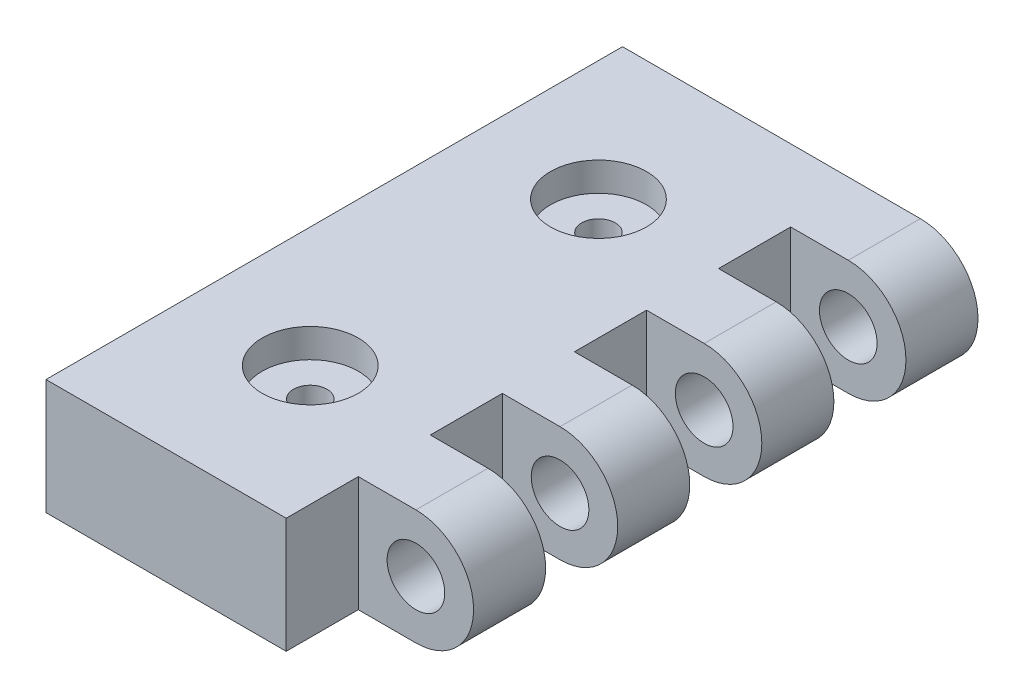
SolidWorks part; units mm, degrees
ref_plane "Front" through (0, 0, 0) normal (0, 0, 1) x (1, 0, 0)
ref_plane "Top" through (0, 0, 0) normal (0, 1, 0) x (1, 0, 0)
ref_plane "Right" through (0, 0, 0) normal (1, 0, 0) x (0, 0, -1)
sketch "Sketch1" plane through (0, 0, 0) normal (0, 1, 0) x (1, 0, 0)
  line L1 (0, 0) -> (-25, 0)
  line L2 (0, 0) -> (0, 60)
  line L3 (0, 60) -> (-25, 60)
  line L4 (-25, 0) -> (-25, 60)
  dimension "D1" = 60
  dimension "D2" = 25
extrude "Boss-Extrude1" add sketch "Sketch1" along normal blind 12
sketch "Sketch2" plane through (0, 0, 0) normal (0, 0, 1) x (1, 0, 0)
  line L0 (0, 0) -> (13.9056, 0) construction
  line L1 (0, 12) -> (0, 0) construction
  line L2 (0, 6) -> (0, 0)
  line L3 (0, 0) -> (6, 0)
  line L4 (0, 6) -> (0, 12)
  line L5 (0, 12) -> (6, 12)
  arc A0 (6, 0) -> (6, 12) centre (6, 6) ccw
  circle A1 centre (6, 6) radius 3
  dimension "D1" = 12
  dimension "D2" = 6
extrude "Boss-Extrude2" add sketch "Sketch2" against normal up to surface (60 mm away) up to face at (-12.5, 6, -60)
sketch "Sketch3" plane through (0, 12, 0) normal (0, 1, 0) x (1, 0, 0)
  line L1 (0, 52.5) -> (12, 52.5)
  line L2 (0, 52.5) -> (0, 45)
  line L3 (0, 45) -> (12, 45)
  line L4 (12, 52.5) -> (12, 45)
  line L5 (12, 0) -> (12, 60) construction
  line L6 (6, 60) -> (-25, 60) construction
  dimension "D1" = 12
  dimension "D2" = 7.5
  dimension "7.5" = 7.5
extrude "Cut-Extrude1" cut sketch "Sketch3" against normal through all
pattern_linear "LPattern1" count 4 spacing 15 along (0, 0, 1) of "Cut-Extrude1"
sketch "Sketch4" plane through (0, 12, 0) normal (0, 1, 0) x (1, 0, 0)
  line L1 (6, 60) -> (-25, 60) construction
  line L2 (-25, 0) -> (0, 0) construction
  line L3 (-12.5, 0) -> (-12.5, 45) construction
  circle A0 centre (-12.5, 45) radius 1.75
  circle A1 centre (-12.5, 15) radius 1.75
  dimension "D4" = 3.5
  dimension "D2" = 15
  dimension "D3" = 15
extrude "Cut-Extrude2" cut sketch "Sketch4" against normal through all
sketch "Sketch5" plane through (0, 12, 0) normal (0, 1, 0) x (1, 0, 0)
  circle A0 centre (-12.5, 45) radius 5
  circle A1 centre (-12.5, 15) radius 5
  dimension "D1" = 10
extrude "Cut-Extrude3" cut sketch "Sketch5" against normal blind 3
pattern_linear "LPattern2" count 2 spacing 9 along (0, -1, 0) of "Cut-Extrude3"
